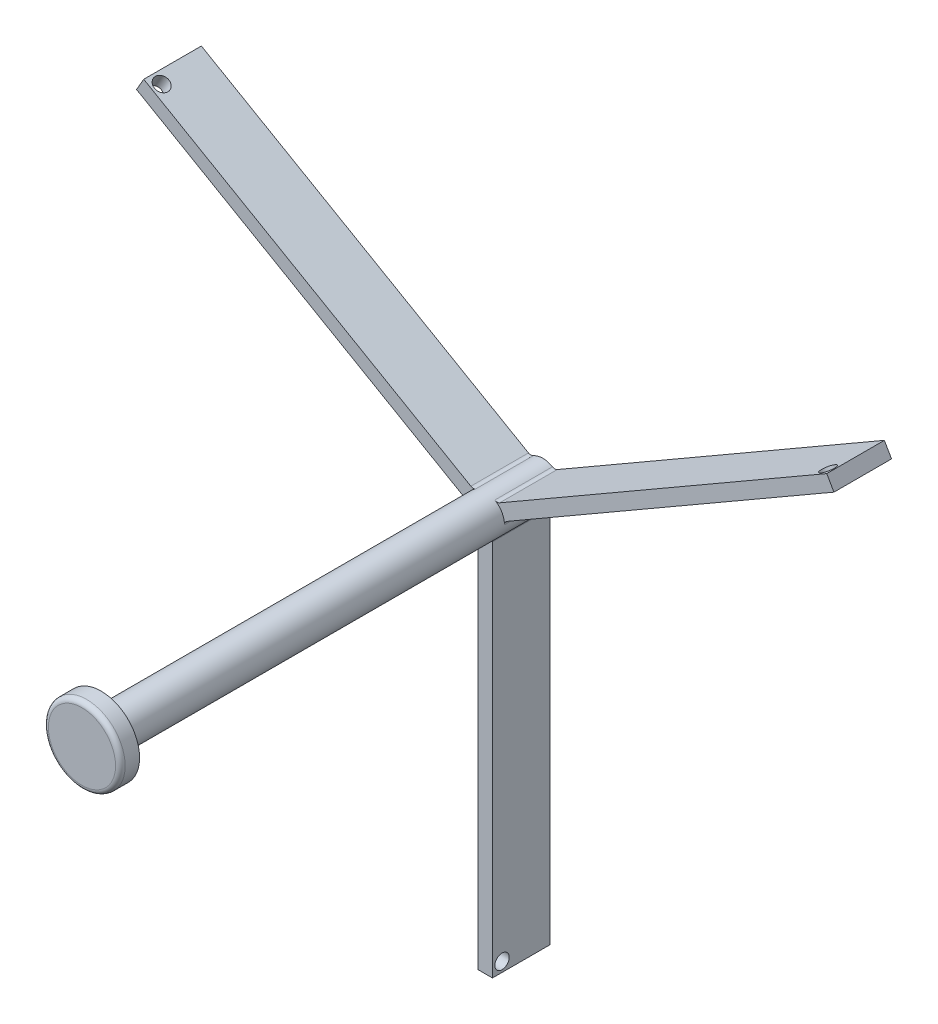
SolidWorks part; units mm, degrees
ref_plane "Plane1" through (0, 0, 0) normal (0, 0, 1) x (1, 0, 0)
ref_plane "Plane2" through (0, 0, 0) normal (0, 1, 0) x (1, 0, 0)
ref_plane "Plane3" through (0, 0, 0) normal (1, 0, 0) x (0, 0, -1)
other "Configuration Table"
sketch "Sketch1" plane through (0, 0, 0) normal (0, 0, 1) x (1, 0, 0)
  circle A0 centre (0, 0) radius 12.7
  dimension "D1" = 25.4
extrude "Base-Extrude" add sketch "Sketch1" along normal blind 304.8
sketch "Sketch2" plane through (0, 0, 0) normal (0, 1, 0) x (1, 0, 0)
  line L0 (0, 0) -> (0, -56.9618) construction
  line L1 (4.7625, 0) -> (-4.7625, 0)
  line L2 (12.7, 0) -> (-12.7, 0) construction
  line L3 (-4.7625, 0) -> (-4.7625, -38.1)
  line L4 (4.7625, 0) -> (4.7625, -38.1)
  line L5 (-4.7625, -38.1) -> (4.7625, -38.1)
  point P7 (0, 0)
  point P11 (0, -38.1)
  dimension "D1" = 38.1
  dimension "D2" = 9.525
extrude "Boss-Extrude1" add sketch "Sketch2" against normal blind 263.525
sketch "Sketch3" plane through (-4.7625, 0, 0) normal (-1, 0, 0) x (0, 0, 1)
  line L0 (0, -263.525) -> (38.1, -263.525) construction
  line L1 (38.1, -263.525) -> (38.1, -11.7732) construction
  circle A0 centre (31.75, -257.175) radius 4.7625
  dimension "D1" = 9.525
  dimension "D2" = 6.35
  dimension "D3" = 6.35
extrude "Cut-Extrude1" cut sketch "Sketch3" against normal through all
pattern_circular "CirPattern1" count 3 every 120 about axis through (0, 0, 0) along (0, 0, 1) of "Boss-Extrude1"
sketch "Sketch4" plane through (-194.3928, 106.7334, 225.0677) normal (-0.5, -0.866, 0) x (0.866, -0.5, 0)
  line L0 (-41.8092, -225.0677) -> (-41.8092, -186.9677) construction
  line L1 (-41.8092, -186.9677) -> (209.9426, -186.9677) construction
  circle A0 centre (-35.4592, -193.3177) radius 4.7625
  dimension "D1" = 9.525
  dimension "D2" = 6.35
  dimension "D3" = 6.35
extrude "Cut-Extrude2" cut sketch "Sketch4" against normal through all
sketch "Sketch5" plane through (132.0101, 70.7168, 223.486) normal (0.5, -0.866, 0) x (0.866, 0.5, 0)
  line L0 (113.8425, -223.486) -> (113.8425, -185.386) construction
  line L1 (113.8425, -185.386) -> (-137.9093, -185.386) construction
  circle A0 centre (107.4925, -191.736) radius 4.7625
  dimension "D1" = 9.525
  dimension "D2" = 6.35
  dimension "D3" = 6.35
extrude "Cut-Extrude3" cut sketch "Sketch5" against normal through all
hole_wizard "Hole1" positions "Sketch7" profile "Sketch8" legacy
sketch "Sketch7" plane through (0, 0, 0) normal (0, 0, -1) x (-1, 0, 0)
  point P0 (0, -63.5)
  dimension "D1" = 63.5
sketch "Sketch8" plane through (0, -63.5, 0) normal (1, 0, 0) x (0, 1, 0)
  line L0 (0, 0) -> (0, 8.6166)
  line L1 (0, 8.6166) -> (1.1303, 7.9375)
  line L2 (1.1303, 7.9375) -> (1.1303, 6.35)
  line L3 (1.1303, 6.35) -> (1.4224, 6.35)
  line L4 (1.4224, 6.35) -> (1.4224, 0.0025)
  line L5 (1.4224, 0.0025) -> (1.4224, 0)
  line L6 (1.4224, 0) -> (0, 0)
hole_wizard "Hole2" positions "Sketch9" profile "Sketch10" legacy
sketch "Sketch9" plane through (0, 0, 0) normal (0, 0, -1) x (-1, 0, 0)
  point P0 (0, -139.7)
  dimension "D1" = 139.7
sketch "Sketch10" plane through (0, -139.7, 0) normal (1, 0, 0) x (0, 1, 0)
  line L0 (0, 0) -> (0, 8.6166)
  line L1 (0, 8.6166) -> (1.1303, 7.9375)
  line L2 (1.1303, 7.9375) -> (1.1303, 6.35)
  line L3 (1.1303, 6.35) -> (1.4224, 6.35)
  line L4 (1.4224, 6.35) -> (1.4224, 0.0025)
  line L5 (1.4224, 0.0025) -> (1.4224, 0)
  line L6 (1.4224, 0) -> (0, 0)
hole_wizard "Hole3" positions "Sketch11" profile "Sketch12" legacy
sketch "Sketch11" plane through (0, 0, 0) normal (0, 0, -1) x (-1, 0, 0)
  point P0 (0, -215.9)
  dimension "D1" = 215.9
sketch "Sketch12" plane through (0, -215.9, 0) normal (1, 0, 0) x (0, 1, 0)
  line L0 (0, 0) -> (0, 8.6166)
  line L1 (0, 8.6166) -> (1.1303, 7.9375)
  line L2 (1.1303, 7.9375) -> (1.1303, 6.35)
  line L3 (1.1303, 6.35) -> (1.4224, 6.35)
  line L4 (1.4224, 6.35) -> (1.4224, 0.0025)
  line L5 (1.4224, 0.0025) -> (1.4224, 0)
  line L6 (1.4224, 0) -> (0, 0)
pattern_circular "CirPattern2" count 3 every 120 about axis through (0, 0, 0) along (0, 0, 1) of "Hole3", "Hole2", "Hole1"
fillet "Fillet1" radius 3.175 2 edges at (-12.5772, 1.7622, 19.05) (-4.7625, -11.7732, 19.05)
fillet "Fillet2" radius 3.175 2 edges at (7.8147, 10.0111, 19.05) (-7.8147, 10.0111, 19.05)
fillet "Fillet3" radius 3.175 2 edges at (12.5772, 1.7622, 19.05) (4.7625, -11.7732, 19.05)
sketch "Sketch13" plane through (0, 0, 304.8) normal (0, 0, 1) x (1, 0, 0)
  circle A0 centre (0, 0) radius 25.4
  circle A3 centre (0, 0) radius 12.7 construction
  dimension "D1" = 12.7
extrude "Extrude1" add sketch "Sketch13" against normal blind 12.7
fillet "Fillet4" radius 3.175 1 edges at (25.4, 0, 304.8)
